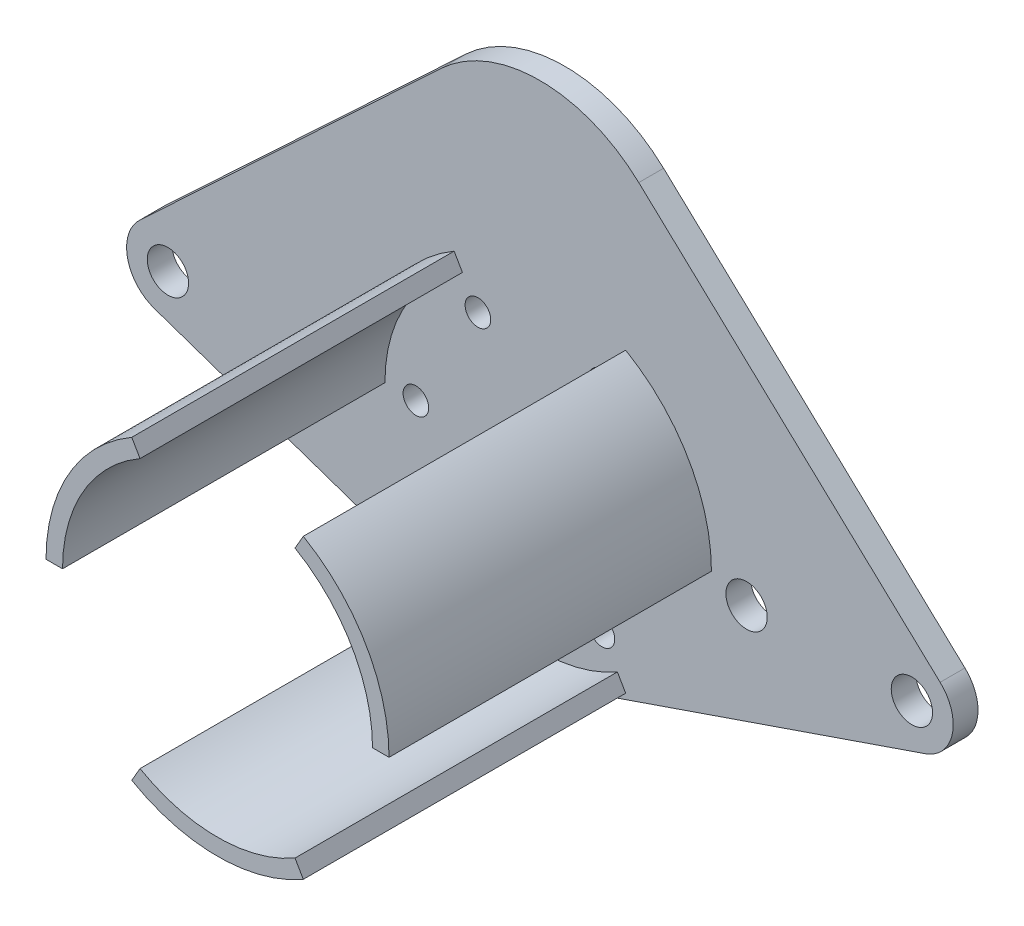
SolidWorks part; units mm, degrees
ref_plane "Front Plane" through (0, 0, 0) normal (0, 0, 1) x (1, 0, 0)
ref_plane "Top Plane" through (0, 0, 0) normal (0, 1, 0) x (1, 0, 0)
ref_plane "Right Plane" through (0, 0, 0) normal (1, 0, 0) x (0, 0, -1)
sketch "Sketch1" plane through (0, 0, 0) normal (0, 0, 1) x (1, 0, 0)
  line L0 (0, 25) -> (0, 0) construction
  line L1 (0, 1.4545) -> (-18.5, 1.4545) construction
  line L2 (-7.5, 14.4449) -> (0, 1.4545) construction
  line L3 (-7.5, -11.5359) -> (0, 1.4545) construction
  line L4 (-45, 0) -> (0, 0) construction
  line L5 (-46.6249, -4.7286) -> (-6.8247, -18.4056)
  line L6 (-48.4169, 3.6504) -> (-11.959, 37.7762)
  line L7 (46.6249, -4.7286) -> (6.8247, -18.4056)
  line L8 (48.4169, 3.6504) -> (11.959, 37.7762)
  circle A0 centre (-25, 0) radius 2.5
  circle A1 centre (0, 1.4545) radius 18.5 construction
  circle A2 centre (0, -5.5455) radius 6.1
  circle A3 centre (0, 1.4545) radius 15 construction
  circle A4 centre (-7.5, 14.4449) radius 1.55
  circle A5 centre (-15, 1.4545) radius 1.55
  circle A6 centre (-7.5, -11.5359) radius 1.55
  circle A7 centre (-45, 0) radius 5 construction
  circle A8 centre (0, 25) radius 17.5 construction
  circle A9 centre (0, 1.4545) radius 21 construction
  arc A10 (-48.4169, 3.6504) -> (-46.6249, -4.7286) centre (-45, 0) ccw
  circle A11 centre (7.5, -11.5359) radius 1.55
  circle A12 centre (7.5, 14.4449) radius 1.55
  circle A13 centre (15, 1.4545) radius 1.55
  circle A14 centre (25, 0) radius 2.5
  arc A15 (48.4169, 3.6504) -> (46.6249, -4.7286) centre (45, 0) cw
  arc A16 (-11.959, 37.7762) -> (11.959, 37.7762) centre (0, 25) cw
  arc A17 (6.8247, -18.4056) -> (-6.8247, -18.4056) centre (0, 1.4545) cw
  circle A18 centre (-45, 0) radius 2.5
  circle A19 centre (45, 0) radius 2.5
  dimension "D1" = 5
  dimension "D2" = 50
  dimension "D3" = 37
  dimension "D5" = 12.2
  dimension "D9" = 3.1
  dimension "D10" = 30
  dimension "D12" = 10
  dimension "D13" = 35
  dimension "D15" = 42
  dimension "D16" = 5
  dimension "D4" = 1.4545
  dimension "D6" = 7
  dimension "D7" = 60
  dimension "D8" = 60
  dimension "D11" = 45
  dimension "D14" = 25
extrude "Boss-Extrude1" add sketch "Sketch1" along normal blind 3
sketch "Sketch2" plane through (0, 0, 3) normal (0, 0, 1) x (1, 0, 0)
  line L0 (0, 0) -> (0, 22.2045) construction
  line L1 (0, 1.4545) -> (-10.375, -16.5155) construction
  line L2 (0, 1.4545) -> (10.375, -16.5155) construction
  line L3 (0, 1.4545) -> (-20.75, 1.4545) construction
  line L4 (0, 1.4545) -> (-10.375, 19.4245) construction
  line L5 (-10.375, 19.4245) -> (-9.375, 17.6925)
  line L6 (-20.75, 1.4545) -> (-18.75, 1.4545)
  line L7 (-10.375, -16.5155) -> (-9.375, -14.7835)
  line L8 (10.375, -16.5155) -> (9.375, -14.7835)
  line L9 (10.375, 19.4245) -> (9.375, 17.6925)
  line L10 (20.75, 1.4545) -> (18.75, 1.4545)
  circle A0 centre (0, 1.4545) radius 18.5 construction
  circle A1 centre (0, 1.4545) radius 18.5 construction
  circle A2 centre (0, 1.4545) radius 18.75 construction
  circle A3 centre (0, 1.4545) radius 20.75 construction
  arc A4 (-20.75, 1.4545) -> (-10.375, 19.4245) centre (0, 1.4545) cw
  arc A5 (-18.75, 1.4545) -> (-9.375, 17.6925) centre (0, 1.4545) cw
  arc A6 (-9.375, -14.7835) -> (9.375, -14.7835) centre (0, 1.4545) ccw
  arc A7 (-10.375, -16.5155) -> (10.375, -16.5155) centre (0, 1.4545) ccw
  arc A8 (20.75, 1.4545) -> (10.375, 19.4245) centre (0, 1.4545) ccw
  arc A9 (18.75, 1.4545) -> (9.375, 17.6925) centre (0, 1.4545) ccw
  dimension "D1" = 37.5
  dimension "D2" = 2
  dimension "D3" = 150
  dimension "D4" = 150
  dimension "D5" = 60
  dimension "D6" = 60
extrude "Boss-Extrude2" add sketch "Sketch2" along normal blind 39 contours L6 A5 L5 A4 | L7 A7 L8 A6 | A9 L10 A8 L9 region at (-16.3471, 10.8925, 3) region at (0, -17.4215, 3) region at (16.3471, 10.8925, 3)
equation "\"D4@Sketch2\"=\"D3@Sketch2\""
